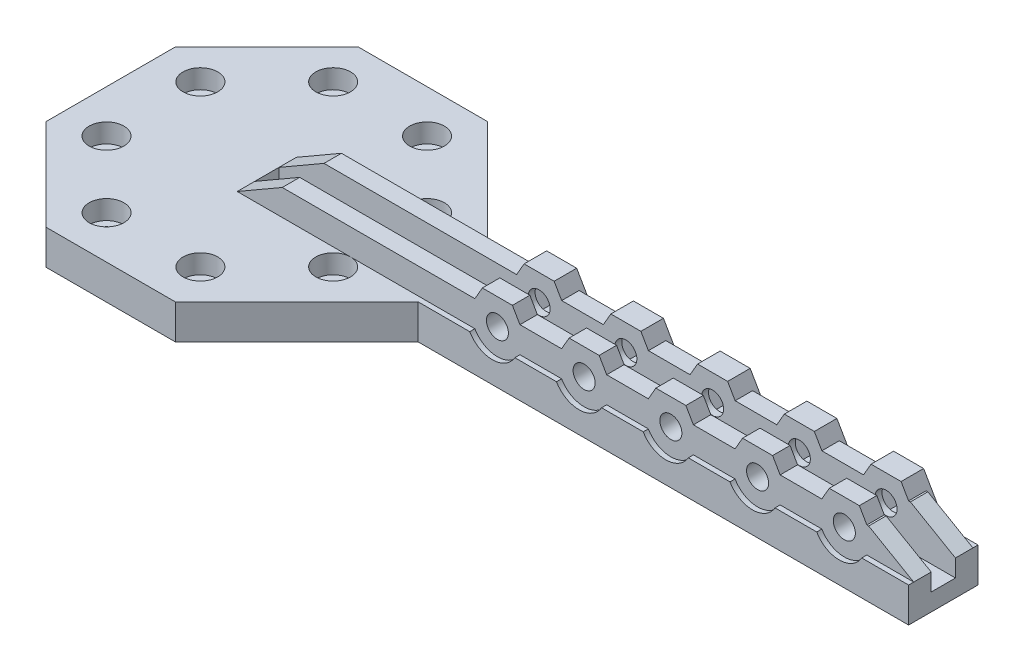
SolidWorks part; units mm, degrees
ref_plane "Front Plane" through (0, 0, 0) normal (0, 0, 1) x (1, 0, 0)
ref_plane "Top Plane" through (0, 0, 0) normal (0, 1, 0) x (1, 0, 0)
ref_plane "Right Plane" through (0, 0, 0) normal (1, 0, 0) x (0, 0, -1)
sketch "Sketch1" plane through (0, 0, 0) normal (0, 1, 0) x (1, 0, 0)
  line L0 (45, 18.6396) -> (63.6396, 0)
  line L7 (45, 18.6396) -> (18.6396, 45)
  line L8 (18.6396, 45) -> (-18.6396, 45)
  line L9 (-18.6396, 45) -> (-45, 18.6396)
  line L10 (-45, 18.6396) -> (-45, -18.6396)
  line L11 (-45, -18.6396) -> (-18.6396, -45)
  line L12 (-18.6396, -45) -> (18.6396, -45)
  line L13 (18.6396, -45) -> (45, -18.6396)
  line L14 (45, -18.6396) -> (45, 18.6396) construction
  line L15 (63.6396, 0) -> (45, -18.6396)
  circle A0 centre (0, 0) radius 45 construction
  point P14 (45, 0)
  dimension "D1" = 45
extrude "Boss-Extrude1" add sketch "Sketch1" against normal blind 10
sketch "Sketch4" plane through (0, 0, 0) normal (0, 1, 0) x (1, 0, 0)
  line L1 (0, 0) -> (-45, -18.6396) construction
  line L2 (-45, -18.6396) -> (-18.6396, -45) construction
  line L3 (0, 0) -> (63.6396, 0) construction
  circle A0 centre (0, 0) radius 45 construction
sketch "Sketch2" plane through (0, 0, 0) normal (0, 1, 0) x (1, 0, 0)
  line L0 (0, 0) -> (-45, -18.6396) construction
  circle A0 centre (-32.6641, -13.5299) radius 2.85
  circle A1 centre (-32.6641, 13.5299) radius 2.85
  circle A2 centre (-13.5299, 32.6641) radius 2.85
  circle A3 centre (13.5299, 32.6641) radius 2.85
  circle A4 centre (32.6641, 13.5299) radius 2.85
  circle A5 centre (32.6641, -13.5299) radius 2.85
  circle A6 centre (13.5299, -32.6641) radius 2.85
  circle A7 centre (-13.5299, -32.6641) radius 2.85
  point P20 (0, 0)
  dimension "D3" = 5.7
  dimension "D1" = 50
  dimension "D2" = 8
extrude "Cut-Extrude1" cut sketch "Sketch2" against normal blind 14
sketch "Sketch5" plane through (0, 0, 0) normal (0, 1, 0) x (1, 0, 0)
  circle A0 centre (-32.6641, -13.5299) radius 5
  circle A1 centre (-32.6641, 13.5299) radius 5
  circle A2 centre (-13.5299, 32.6641) radius 5
  circle A3 centre (13.5299, 32.6641) radius 5
  circle A4 centre (32.6641, 13.5299) radius 5
  circle A5 centre (32.6641, -13.5299) radius 5
  circle A6 centre (13.5299, -32.6641) radius 5
  circle A7 centre (-13.5299, -32.6641) radius 5
  point P19 (0, 0)
  point P21 (0, 0)
  point P22 (0, 0)
  point P23 (0, 0)
  point P24 (0, 0)
  point P25 (0, 0)
  point P26 (0, 0)
  point P27 (0, 0)
  dimension "D1" = 10
  dimension "D2" = 8
extrude "Cut-Extrude2" cut sketch "Sketch5" against normal blind 5.5
sketch "Sketch7" plane through (0, 0, 0) normal (0, 1, 0) x (1, 0, 0)
  line L1 (45, 10) -> (195, 10)
  line L2 (45, 10) -> (45, -10)
  line L3 (45, -10) -> (195, -10)
  line L4 (195, 10) -> (195, -10)
  circle A0 centre (0, 0) radius 45 construction
  point P6 (195, 0)
  dimension "D1" = 150
  dimension "D2" = 20
extrude "Boss-Extrude3" add sketch "Sketch7" against normal blind 10
sketch "Sketch8" plane through (0, 0, 0) normal (0, 1, 0) x (1, 0, 0)
  line L1 (0, -3.5) -> (195, -3.5)
  line L2 (0, -3.5) -> (0, -8.5299)
  line L3 (0, -8.5299) -> (195, -8.5299)
  line L4 (195, -3.5) -> (195, -8.5299)
  line L6 (195, -10) -> (195, 10) construction
  line L7 (-5.5, 0) -> (5.5, 0) construction
  line L8 (0, 8.5299) -> (195, 8.5299)
  line L9 (195, 3.5) -> (195, 8.5299)
  line L10 (0, 3.5) -> (195, 3.5)
  line L11 (0, 3.5) -> (0, 8.5299)
  circle A0 centre (32.6641, -13.5299) radius 5 construction
  dimension "D1" = 3.5
ref_plane "Plane1" through (0, 0.5, 0) normal (0, 1, 0) x (1, 0, 0)
extrude "Boss-Extrude4" add sketch "Sketch8" along normal blind 7.5
sketch "Sketch13" plane through (0, 0, -8.5299) normal (0, 0, -1) x (-1, 0, 0)
  line L0 (-195, 0) -> (-53.6396, 0) construction
  line L1 (-170.6699, -3.75) -> (-166.3397, 3.75) construction
  line L2 (-166.3397, 3.75) -> (-170.6699, 11.25)
  line L3 (-170.6699, 11.25) -> (-179.3301, 11.25)
  line L4 (-179.3301, 11.25) -> (-183.6603, 3.75)
  line L5 (-183.6603, 3.75) -> (-179.3301, -3.75) construction
  line L6 (-179.3301, -3.75) -> (-170.6699, -3.75) construction
  line L7 (-183.6603, 3.75) -> (-183.6603, -3.75)
  line L8 (-195, 7.5) -> (0, 7.5) construction
  line L9 (-168.9378, 3.75) -> (-171.9689, 9)
  line L10 (-171.9689, 9) -> (-178.0311, 9)
  line L11 (-178.0311, 9) -> (-181.0622, 3.75)
  line L12 (-181.0622, 3.75) -> (-178.0311, -1.5)
  line L13 (-178.0311, -1.5) -> (-171.9689, -1.5)
  line L14 (-171.9689, -1.5) -> (-168.9378, 3.75)
  line L15 (-183.6603, -3.75) -> (-166.3397, -3.75)
  line L16 (-166.3397, -3.75) -> (-166.3397, 3.75)
  circle A0 centre (-175, 3.75) radius 7.5 construction
  circle A1 centre (-175, 3.75) radius 5.25 construction
  dimension "D1" = 15
  dimension "D2" = 175
  dimension "D3" = 3.75
  dimension "D4" = 10.5
extrude "Boss-Extrude5" add sketch "Sketch13" along normal up to surface and the other way up to surface up to face at (124.3198, -5, -10) other way up to face at (97.5, 3.75, -3.5)
sketch "Sketch9" plane through (0, 0, 8.5299) normal (0, 0, 1) x (1, 0, 0)
  line L0 (0, 0) -> (12.9904, 7.5)
  line L1 (0, 7.5) -> (195, 7.5) construction
  line L2 (0, 7.5) -> (12.9904, 7.5)
  line L3 (182.0096, 7.5) -> (195, 0)
  line L4 (195, 0) -> (195, 7.5)
  line L5 (195, 7.5) -> (182.0096, 7.5)
  line L6 (0, 0) -> (0, 7.5)
  dimension "D1" = 60
  dimension "D2" = 60
extrude "Cut-Extrude3" cut sketch "Sketch9" against normal up to surface (17.0598 mm away) up to face at (88.9747, 3.125, -8.5299)
sketch "Sketch10" plane through (0, 0, 0) normal (0, 1, 0) x (1, 0, 0)
  line L1 (195, -3.5) -> (0, -3.5)
  line L2 (195, -3.5) -> (195, 3.5)
  line L3 (195, 3.5) -> (0, 3.5)
  line L4 (0, -3.5) -> (0, 3.5)
  dimension "D1" = 7
extrude "Cut-Extrude4" cut sketch "Sketch10" against normal blind 5
sketch "Sketch11" plane through (0, 0, 8.5299) normal (0, 0, 1) x (1, 0, 0)
  circle A0 centre (175, 3.75) radius 3.175
  dimension "D1" = 175
  dimension "D3" = 6.35
  dimension "D2" = 3.75
extrude "Cut-Extrude5" cut sketch "Sketch11" against normal blind 23
sketch "Sketch12" plane through (0, 0, 10) normal (0, 0, 1) x (1, 0, 0)
  circle A0 centre (175, 3.75) radius 7.5
  dimension "D1" = 15
extrude "Cut-Extrude6" cut sketch "Sketch12" against normal up to surface (1.4701 mm away) up to face at (178.175, 3.75, 8.5299)
sketch "Sketch14" plane through (0, 7.5, 0) normal (0, 1, 0) x (1, 0, 0)
  line L4 (171.1029, 3.5) -> (178.8971, 3.5)
  line L5 (178.8971, 3.5) -> (178.8971, 8.5299)
  line L6 (178.8971, 8.5299) -> (171.1029, 8.5299)
  line L7 (171.1029, 8.5299) -> (171.1029, 3.5)
  line L8 (171.1029, 3.5) -> (178.8971, 3.5)
  line L9 (178.8971, 3.5) -> (178.8971, 8.5299)
  line L10 (178.8971, 8.5299) -> (171.1029, 8.5299)
  line L11 (171.1029, 8.5299) -> (171.1029, 3.5)
  dimension "D1" = 0
extrude "Boss-Extrude6" add sketch "Sketch14" along normal up to surface (1.5 mm away) up to face at (175, 9, -6.75)
sketch "Sketch15" plane through (0, 0, -10) normal (0, 0, -1) x (-1, 0, 0)
  line L1 (-168.9378, 3.75) -> (-171.9689, 9)
  line L2 (-171.9689, 9) -> (-178.0311, 9)
  line L3 (-178.0311, 9) -> (-181.0622, 3.75)
  line L4 (-181.0622, 3.75) -> (-178.0311, -1.5)
  line L5 (-178.0311, -1.5) -> (-171.9689, -1.5)
  line L6 (-171.9689, -1.5) -> (-168.9378, 3.75)
  circle A0 centre (-175, 3.75) radius 5.25 construction
extrude "Cut-Extrude7" cut sketch "Sketch15" against normal offset from surface (4.5 mm away) 2 up to face at (171.825, 3.75, -3.5)
sketch "Sketch16" plane through (0, 0, 8.5299) normal (0, 0, 1) x (1, 0, 0)
  line L0 (168.5048, 7.5) -> (170.6699, 11.25)
  line L1 (170.6699, 11.25) -> (179.3301, 11.25)
  line L2 (179.3301, 11.25) -> (181.4952, 7.5)
  line L3 (181.4952, 7.5) -> (168.5048, 7.5)
extrude "Boss-Extrude7" add sketch "Sketch16" against normal up to surface (5.0299 mm away) up to face at (178.175, 3.75, 3.5)
pattern_linear "LPattern4" count 5 spacing 25 along (-1, 0, 0) of "Boss-Extrude5", "Cut-Extrude5", "Cut-Extrude6", "Boss-Extrude6", "Cut-Extrude7", "Boss-Extrude7"
